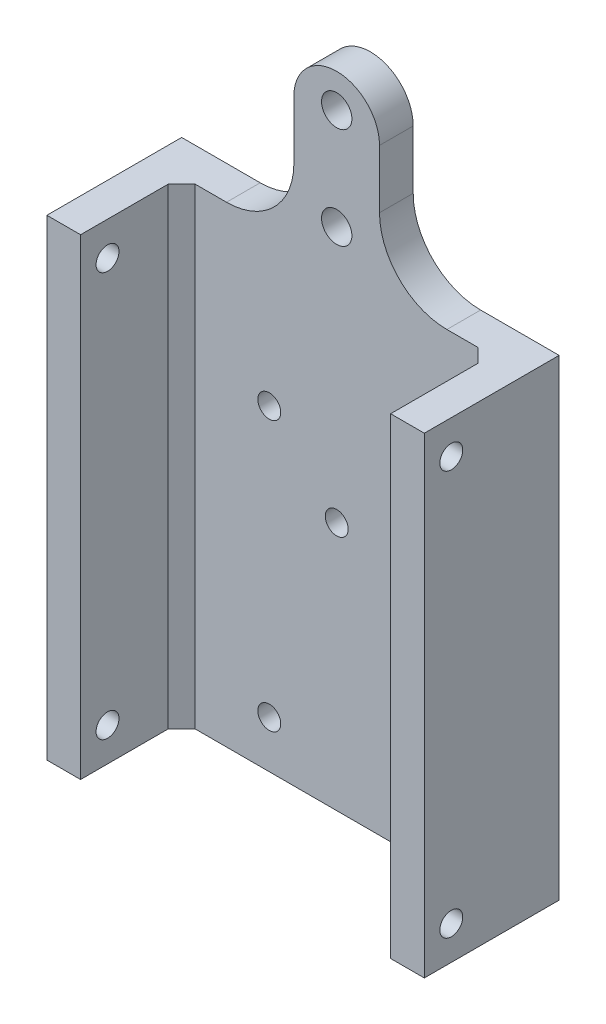
SolidWorks part; units mm, degrees
ref_plane "Front Plane" through (0, 0, 0) normal (0, 0, 1) x (1, 0, 0)
ref_plane "Top Plane" through (0, 0, 0) normal (0, 1, 0) x (1, 0, 0)
ref_plane "Right Plane" through (0, 0, 0) normal (1, 0, 0) x (0, 0, -1)
sketch "Sketch1" plane through (0, 0, 0) normal (0, 1, 0) x (1, 0, 0)
  line L1 (6.35, 2.5) -> (-6.35, 2.5)
  line L2 (6.35, 2.5) -> (6.35, -2.5)
  line L3 (6.35, -2.5) -> (-6.35, -2.5)
  line L4 (-6.35, 2.5) -> (-6.35, -2.5)
  line L5 (6.35, 2.5) -> (-6.35, -2.5) construction
  line L6 (6.35, -2.5) -> (-6.35, 2.5) construction
  point P0 (0, 0)
  dimension "D1" = 5
  dimension "D2" = 12.7
extrude "Boss-Extrude1" add sketch "Sketch1" along normal blind 25
hole_wizard "M4 Clearance Hole1" positions "Sketch2" profile "Sketch3" hole size "M4" standard "ANSI Metric" end condition through all
sketch "Sketch2" plane through (0, 0, 2.5) normal (0, 0, 1) x (1, 0, 0)
  line L0 (-6.35, 0) -> (6.35, 0) construction
  point P0 (0, 5)
  point P2 (0, 20)
  point P8 (0, 0)
  dimension "D1" = 15
  dimension "D2" = 5
sketch "Sketch3" plane through (0, 5, 2.5) normal (1, 0, 0) x (0, -1, 0)
  line L0 (0, 0) -> (0, 5)
  line L1 (0, 5) -> (2.25, 5)
  line L2 (2.25, 5) -> (2.25, 0)
  line L5 (2.25, 0) -> (0, 0)
  line L11 (0, -6.35) -> (0, 107.95) construction
  dimension "Thru Hole Dia." = 4.5
  dimension "Thru Hole Depth" = 5
sketch "Sketch4" plane through (0, 0, 0) normal (0, 1, 0) x (1, 0, 0)
  line L0 (-6.35, -2.5) -> (6.35, -2.5) construction
  line L1 (-23, 2.5) -> (23, 2.5)
  line L2 (-23, 2.5) -> (-23, -2.5)
  line L3 (-23, -2.5) -> (23, -2.5)
  line L4 (23, 2.5) -> (23, -2.5)
  line L5 (0, -2.5) -> (0, 2.5) construction
  line L6 (-23, 0) -> (23, 0) construction
  line L7 (6.35, 2.5) -> (-6.35, 2.5) construction
  point P412 (0, 0)
  dimension "D2" = 46
extrude "Boss-Extrude2" add sketch "Sketch4" against normal blind 70
sketch "Sketch5" plane through (0, 0, 0) normal (0, 1, 0) x (1, 0, 0)
  line L0 (0, 0) -> (0, -2.5) construction
  line L1 (-6.35, -2.5) -> (6.35, -2.5) construction
  line L2 (-23, -7.5) -> (-28, -7.5) construction
  line L3 (23, 2.5) -> (28, 2.5)
  line L4 (23, 2.5) -> (23, -17.5)
  line L5 (23, -17.5) -> (28, -17.5)
  line L6 (28, 2.5) -> (28, -17.5)
  line L7 (25.5, -17.5) -> (25.5, 2.5) construction
  line L8 (23, -7.5) -> (28, -7.5) construction
  line L9 (-25.5, -17.5) -> (-25.5, 2.5) construction
  line L10 (-28, 2.5) -> (-28, -17.5)
  line L11 (-23, -17.5) -> (-28, -17.5)
  line L12 (-23, 2.5) -> (-23, -17.5)
  line L13 (-23, 2.5) -> (-28, 2.5)
  point P17 (-25.5, -7.5)
  point P261 (25.5, -7.5)
  dimension "D1" = 20
  dimension "D2" = 5
extrude "Boss-Extrude3" add sketch "Sketch5" against normal blind 70
hole_wizard "M3 Clearance Hole1" positions "Sketch6" profile "Sketch7" hole size "M3" standard "ANSI Metric" end condition through all
sketch "Sketch6" plane through (28, 0, 0) normal (1, 0, 0) x (0, 0, -1)
  line L0 (-17.5, -35) -> (2.5, -35) construction
  line L1 (-17.5, -70) -> (-17.5, 0) construction
  line L2 (2.5, -70) -> (2.5, 0) construction
  line L4 (-2.5, 25) -> (-2.5, 0) construction
  point P0 (-13.5, -5)
  point P2 (-13.5, -65)
  dimension "D1" = 60
  dimension "D2" = 11
sketch "Sketch7" plane through (28, -5, 13.5) normal (0, 1, 0) x (0, 0, -1)
  line L0 (0, 0) -> (0, 56)
  line L1 (0, 56) -> (1.7, 56)
  line L2 (1.7, 56) -> (1.7, 0)
  line L5 (1.7, 0) -> (0, 0)
  line L11 (0, -6.35) -> (0, 107.95) construction
  dimension "Thru Hole Dia." = 3.4
  dimension "Thru Hole Depth" = 56
hole_wizard "M3 Clearance Hole2" positions "Sketch8" profile "Sketch9" hole size "M3" standard "ANSI Metric" end condition through all
sketch "Sketch8" plane through (0, 0, -2.5) normal (0, 0, -1) x (-1, 0, 0)
  point P0 (-10, -23)
  point P2 (10, -23)
  point P5 (0, -33)
  point P8 (-10, -63)
  point P11 (10, -63)
sketch "Sketch9" plane through (10, -23, -2.5) normal (1, 0, 0) x (0, 1, 0)
  line L0 (0, 0) -> (0, 20)
  line L1 (0, 20) -> (1.7, 20)
  line L2 (1.7, 20) -> (1.7, 0)
  line L5 (1.7, 0) -> (0, 0)
  line L11 (0, -6.35) -> (0, 107.95) construction
  dimension "Thru Hole Dia." = 3.4
  dimension "Thru Hole Depth" = 20
sketch "Sketch10" plane through (28, 0, 0) normal (1, 0, 0) x (0, 0, -1)
  line L0 (-17.5, -70) -> (-17.5, 0) construction
  line L1 (-17.5, -60) -> (-4.5, -60)
  line L2 (-17.5, -60) -> (-17.5, -10)
  line L3 (-17.5, -10) -> (-4.5, -10)
  line L4 (-4.5, -60) -> (-4.5, -10)
  line L5 (-17.5, 0) -> (2.5, 0) construction
  line L6 (-17.5, -70) -> (2.5, -70) construction
  line L7 (2.5, -70) -> (2.5, 0) construction
  dimension "D1" = 10
  dimension "D2" = 10
  dimension "D3" = 7
extrude "Cut-Extrude1" [suppressed] cut sketch "Sketch10" against normal through all
fillet "Fillet1" 2 edges at (-6.35, 25, 0) (6.35, 25, 0) type full round first side face at (-6.35, 12.5, 0) second side face at (6.35, 12.5, 0) middle face at (0, 25, 0)
fillet "Fillet2" radius 10 2 edges at (-6.35, 0, 0) (6.35, 0, 0)
fillet "Fillet3" [suppressed] radius 7 profile chamfer
fillet "Fillet4" radius 2 2 edges at (23, -35, 2.5) (-23, -35, 2.5) profile chamfer
fillet "Fillet5" [suppressed] type full round
fillet "Fillet6" [suppressed] type full round
fillet "Fillet7" [suppressed] type full round
fillet "Fillet8" [suppressed] type full round
fillet "Fillet9" [suppressed] radius 5
